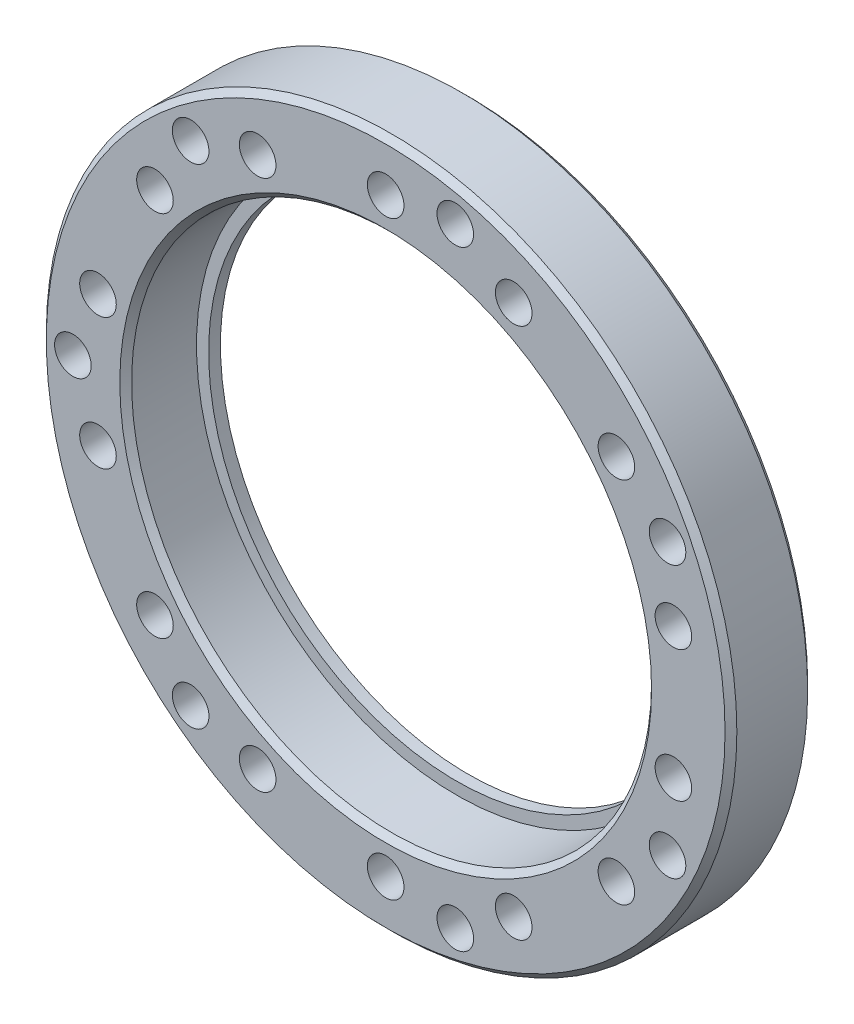
SolidWorks part; units mm, degrees
ref_plane "Front Plane" through (0, 0, 0) normal (0, 0, 1) x (1, 0, 0)
ref_plane "Top Plane" through (0, 0, 0) normal (0, 1, 0) x (1, 0, 0)
ref_plane "Right Plane" through (0, 0, 0) normal (1, 0, 0) x (0, 0, -1)
sketch "Sketch1" plane through (0, 0, 0) normal (0, 0, 1) x (1, 0, 0)
  line L0 (0, 0) -> (0, 42.6293) construction
  circle A0 centre (0, 0) radius 22.025
  circle A1 centre (0, 0) radius 29.25
  circle A2 centre (0, 25) radius 1.55
  circle A3 centre (10.8471, 22.5242) radius 1.55
  circle A4 centre (19.5458, 15.5872) radius 1.55
  circle A5 centre (24.3732, 5.563) radius 1.55
  circle A6 centre (24.3732, -5.563) radius 1.55
  circle A7 centre (19.5458, -15.5872) radius 1.55
  circle A8 centre (10.8471, -22.5242) radius 1.55
  circle A9 centre (0, -25) radius 1.55
  circle A10 centre (-10.8471, -22.5242) radius 1.55
  circle A11 centre (-19.5458, -15.5872) radius 1.55
  circle A12 centre (-24.3732, -5.563) radius 1.55
  circle A13 centre (-24.3732, 5.563) radius 1.55
  circle A14 centre (-19.5458, 15.5872) radius 1.55
  circle A15 centre (-10.8471, 22.5242) radius 1.55
  circle A18 centre (0, 0) radius 20
  point P39 (0, 0)
  dimension "D1" = 58.5
  dimension "D2" = 44.05
  dimension "D3" = 3.1
  dimension "D6" = 40
  dimension "D4" = 25
  dimension "D5" = 14
extrude "Boss-Extrude1" add sketch "Sketch1" along normal blind 7 contours A4 | A5 | A6 | A7 | A8 | A9 | A2 L0 | L0 A2 | A3 | A15 | A14 | A12 | A13 | A11 | A10 | A0 A2 A1 A15 A14 A13 A12 A11 A10 A9 A8 A7 A6 A5 A4 A3 region at (20.0979, 20.0979, 0) region at (-0.6578, 25, 0) region at (0.6578, 25, 0) region at (10.8471, 22.5242, 0) region at (19.5458, 15.5872, 0) region at (24.3732, 5.563, 0) region at (24.3732, -5.563, 0) region at (19.5458, -15.5872, 0) region at (10.8471, -22.5242, 0) region at (0, -25, 0) region at (-10.8471, -22.5242, 0) region at (-19.5458, -15.5872, 0) region at (-24.3732, -5.563, 0) region at (-24.3732, 5.563, 0) region at (-19.5458, 15.5872, 0) region at (-10.8471, 22.5242, 0)
extrude "Cut-Extrude1" cut sketch "Sketch1<3>" against normal blind 4 from surface contours A2 L0 | L0 A2 | A3 | A4 | A5 | A6 | A7 | A8 | A9 | A10 | A11 | A12 | A13 | A14 | A15 region at (-0.6578, 25, 0) region at (0.6578, 25, 0) region at (10.8471, 22.5242, 0) region at (19.5458, 15.5872, 0) region at (24.3732, 5.563, 0) region at (24.3732, -5.563, 0) region at (19.5458, -15.5872, 0) region at (10.8471, -22.5242, 0) region at (0, -25, 0) region at (-10.8471, -22.5242, 0) region at (-19.5458, -15.5872, 0) region at (-24.3732, -5.563, 0) region at (-24.3732, 5.563, 0) region at (-19.5458, 15.5872, 0) region at (-10.8471, 22.5242, 0) starting at face at (29.25, 0, 7)
sketch "Sketch1<3>" plane through (0, 0, 0) normal (0, 0, 1) x (1, 0, 0) same geometry as "Sketch1"
sketch "Sketch4" plane through (0, 0, 0) normal (0, 0, 1) x (1, 0, 0)
  circle A0 centre (0, 0) radius 22.25
  circle A1 centre (0, 0) radius 21
  dimension "D1" = 44.5
  dimension "D2" = 42
extrude "Boss-Extrude2" add sketch "Sketch4" along normal blind 1 from surface starting at face at (29.25, 0, 0)
sketch "Sketch2" plane through (0, 0, 0) normal (0, 0, 1) x (1, 0, 0)
  circle A0 centre (0, 0) radius 24
  circle A1 centre (0, 0) radius 29
  dimension "D1" = 48
  dimension "D2" = 58
sketch "Sketch3" plane through (0, 0, 0) normal (0, 0, 1) x (1, 0, 0)
  line L0 (0, 0) -> (0, 31.0844) construction
  line L1 (0, 0) -> (6.9256, 30.3429) construction
  circle A0 centre (0, 0) radius 26.5 construction
  circle A1 centre (5.8968, 25.8356) radius 1.55
  circle A2 centre (23.8757, 11.4979) radius 1.55
  circle A3 centre (23.8757, -11.4979) radius 1.55
  circle A4 centre (5.8968, -25.8356) radius 1.55
  circle A5 centre (-16.5225, -20.7185) radius 1.55
  circle A6 centre (-26.5, 0) radius 1.55
  circle A7 centre (-16.5225, 20.7185) radius 1.55
  point P23 (0, 0)
  dimension "D2" = 53
  dimension "D3" = 3.1
  dimension "D4" = 7
  dimension "D1" = 12.857
extrude "Cut-Extrude2" cut sketch "Sketch3" along normal through all contours A2 | A1 | A7 | A6 | A5 | A4 | A3 region at (5.8968, 25.8356, 0) region at (23.8757, 11.4979, 0) region at (23.8757, -11.4979, 0) region at (5.8968, -25.8356, 0) region at (-16.5225, -20.7185, 0) region at (-26.5, 0, 0) region at (-16.5225, 20.7185, 0)
chamfer "Chamfer1" distance 0.5 angle 45 3 edges at (22.025, 0, 7) (29.25, 0, 7) (29.25, 0, 0)
